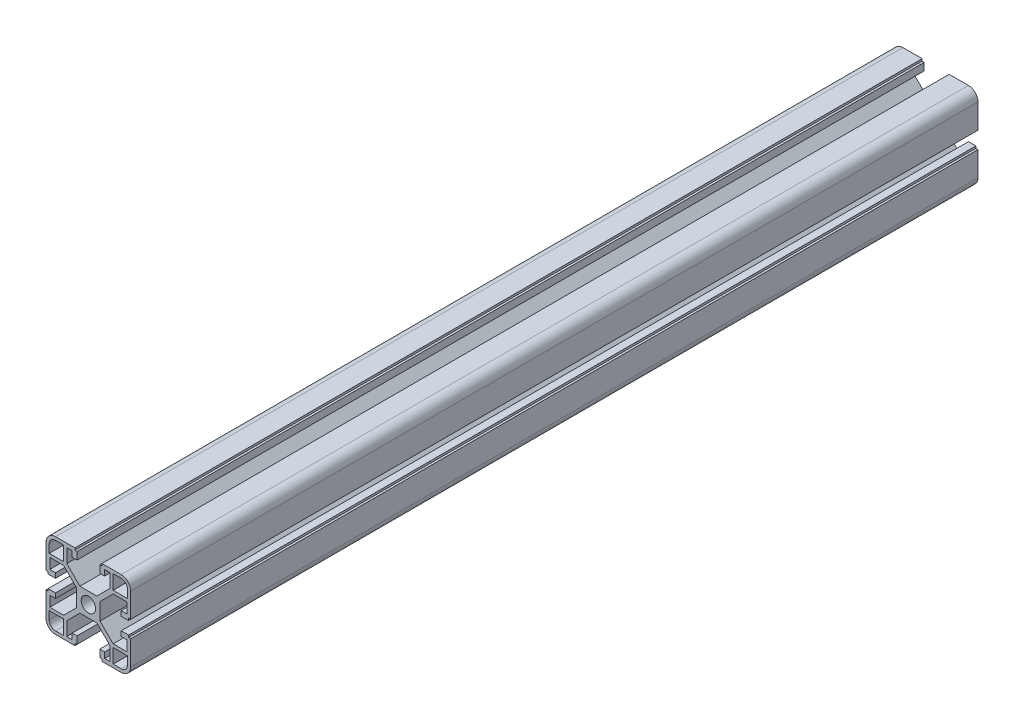
SolidWorks part; units mm, degrees
material "6061-T6 (SS)"
ref_plane "Front Plane" through (0, 0, 0) normal (0, 0, 1) x (1, 0, 0)
ref_plane "Top Plane" through (0, 0, 0) normal (0, 1, 0) x (1, 0, 0)
ref_plane "Right Plane" through (0, 0, 0) normal (1, 0, 0) x (0, 0, -1)
sketch "Sketch1" plane through (0, 0, 0) normal (0, 0, 1) x (1, 0, 0)
  line L0 (3.4, 0) -> (5.5, 0)
  line L1 (10.19, 11.69) -> (4, 5.5)
  line L2 (11.69, 10.19) -> (5.5, 4)
  line L3 (18.2, 10.19) -> (11.69, 10.19)
  line L4 (18.2, 10.19) -> (18.2, 5.2656)
  line L5 (18.2, 5.2656) -> (15.5, 5.2656)
  line L6 (15.5, 5.2656) -> (15.5, 2.9656)
  line L7 (15.5, 2.9656) -> (19, 2.9656)
  line L8 (19, 2.9656) -> (19, 3.9656)
  line L9 (19, 3.9656) -> (20, 3.9656)
  line L10 (20, 3.9656) -> (20, 15.5)
  line L11 (15.5, 20) -> (6.3853, 20)
  line L12 (18.5, 11.69) -> (18.5, 15.5)
  line L13 (15.5, 18.5) -> (11.69, 18.5)
  line L14 (11.69, 11.69) -> (11.69, 18.5)
  line L15 (0, 3.4) -> (0, 5.5)
  line L16 (4, 5.5) -> (0, 5.5)
  line L17 (6.3853, 20) -> (6.3853, 19)
  line L18 (5.5, 0) -> (5.5, 4)
  line L19 (6.3853, 19) -> (5.3853, 19)
  line L20 (5.3853, 19) -> (5.3853, 15.5)
  line L21 (5.3853, 15.5) -> (7.6853, 15.5)
  line L22 (10.19, 11.69) -> (10.19, 18.2)
  line L23 (11.69, 11.69) -> (18.5, 11.69)
  line L24 (7.6853, 18.2) -> (7.6853, 15.5)
  line L25 (10.19, 18.2) -> (7.6853, 18.2)
  arc A0 (20, 15.5) -> (15.5, 20) centre (15.5, 15.5) ccw
  arc A1 (18.5, 15.5) -> (15.5, 18.5) centre (15.5, 15.5) ccw
  arc A2 (3.4, 0) -> (0, 3.4) centre (0, 0) ccw
  dimension "D3" = 4.5
  dimension "D18" = 1.5
  dimension "D9" = 3.4
  dimension "D20" = 1.8
  dimension "D25" = 3
  dimension "D1" = 5.5
  dimension "D2" = 1.5
  dimension "D4" = 14.5
  dimension "D5" = 1.5
  dimension "D6" = 2.1
  dimension "D7" = 2.3
  dimension "D8" = 1.8
  dimension "D10" = 6.81
  dimension "D11" = 2.1
  dimension "D12" = 1
  dimension "D13" = 4.5
  dimension "D14" = 45
  dimension "D15" = 14.5
  dimension "D16" = 1
  dimension "D17" = 1.5
  dimension "D19" = 6.81
  dimension "D21" = 4.5
  dimension "D22" = 2.3
  dimension "D23" = 1
  dimension "D24" = 1
  dimension "D26" = 8.754
  dimension "D27" = 8.754
  dimension "D28" = 4.9244
  dimension "D29" = 2.5047
extrude "Boss-Extrude1" add sketch "Sketch1" along normal blind 400
mirror "Mirror1" about plane through (0, 0, 0) normal (0, 1, 0) of "Boss-Extrude1"
mirror "Mirror2" about plane through (0, 0, 0) normal (1, 0, 0) of "Boss-Extrude1"
mirror "Mirror3" about plane through (0, 0, 0) normal (0, 1, 0) of "Mirror2"
sketch "Croquis2" plane through (0, 0, 400) normal (0, 0, 1) x (1, 0, 0)
  line L0 (-4, 5.5) -> (-5.5, 4)
  line L1 (-5.5, 4) -> (-5.5, -4)
  line L2 (-5.5, -4) -> (-4, -5.5)
  line L3 (-4, -5.5) -> (-4, -28.3763)
  line L4 (-4, -28.3763) -> (-28.3763, -28.3763)
  line L5 (-28.3763, -28.3763) -> (-28.3763, 30.8262)
  line L6 (-28.3763, 30.8262) -> (-4, 30.8262)
  line L7 (-4, 30.8262) -> (-4, 5.5)
extrude "Cortar-Extruir2" [suppressed] cut sketch "Croquis2" against normal blind 70
